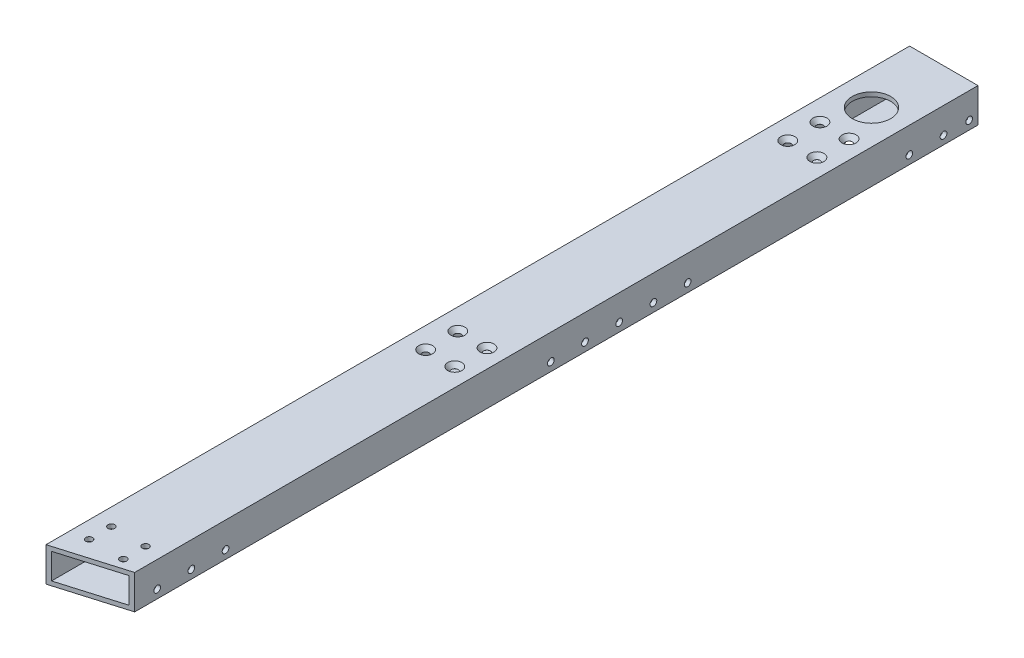
SolidWorks part; units mm, degrees
ref_plane "Front Plane" through (0, 0, 0) normal (0, 0, 1) x (1, 0, 0)
ref_plane "Top Plane" through (0, 0, 0) normal (0, 1, 0) x (1, 0, 0)
ref_plane "Right Plane" through (0, 0, 0) normal (1, 0, 0) x (0, 0, -1)
sketch "Sketch1" plane through (0, 0, 0) normal (0, 0, 1) x (1, 0, 0)
  line L0 (-22.225, 9.525) -> (22.225, 9.525)
  line L2 (-25.4, 12.7) -> (25.4, 12.7)
  line L3 (-25.4, 12.7) -> (-25.4, -12.7)
  line L4 (-25.4, -12.7) -> (25.4, -12.7)
  line L5 (25.4, 12.7) -> (25.4, -12.7)
  line L10 (22.225, 9.525) -> (22.225, -9.525)
  line L11 (-22.225, -9.525) -> (22.225, -9.525)
  line L12 (-22.225, 9.525) -> (-22.225, -9.525)
  point P12 (0, 12.7)
  point P14 (25.4, 0)
  dimension "Wall Thickness" = 3.175
  dimension "Outside Width" = 50.8
  dimension "Outside Height" = 25.4
  dimension "Inside Height" = 19.05
  dimension "Inside Width" = 44.45
sketch "Sketch2" plane through (0, 0, 0) normal (1, 0, 0) x (0, 0, -1)
  line L0 (320.675, 0) -> (-320.675, 0)
  point P4 (0, 0)
  point P7 (-320.675, 0)
  point P10 (320.675, 0)
  dimension "Length" = 641.35
sketch "Sketch3" plane through (0, 0, 0) normal (0, 0, 1) x (1, 0, 0)
  line L21 (25.4, 12.7) -> (-25.4, 12.7)
  line L22 (25.4, -12.7) -> (25.4, 12.7)
  line L23 (-25.4, -12.7) -> (25.4, -12.7)
  line L24 (-25.4, 12.7) -> (-25.4, -12.7)
  line L25 (25.4, 12.7) -> (-25.4, 12.7)
  line L26 (25.4, -12.7) -> (25.4, 12.7)
  line L27 (-25.4, -12.7) -> (25.4, -12.7)
  line L28 (-25.4, 12.7) -> (-25.4, -12.7)
  line L29 (22.225, 9.525) -> (-22.225, 9.525)
  line L30 (22.225, -9.525) -> (22.225, 9.525)
  line L31 (-22.225, -9.525) -> (22.225, -9.525)
  line L32 (-22.225, 9.525) -> (-22.225, -9.525)
  line L33 (22.225, 9.525) -> (-22.225, 9.525)
  line L34 (22.225, -9.525) -> (22.225, 9.525)
  line L35 (-22.225, -9.525) -> (22.225, -9.525)
  line L36 (-22.225, 9.525) -> (-22.225, -9.525)
  dimension "D1" = 0
  dimension "D2" = 0
extrude "Boss-Extrude1" add sketch "Sketch3" along normal up to vertex (320.675 mm away) and the other way up to vertex (320.675 mm away) up to point (0, 0, 320.675) other way up to point (0, 0, -320.675)
sketch "Drawing Reference" plane through (0, 0, 0) normal (1, 0, 0) x (0, 0, -1)
  line L0 (-320.675, 0) -> (320.675, 0) construction
  line L1 (0, -12.7) -> (0, 12.7) construction
  line L2 (-320.675, -12.7) -> (320.675, -12.7) construction
  line L5 (-320.675, 12.7) -> (320.675, 12.7) construction
  point P7 (-284.099, 0)
  point P8 (284.099, 0)
  dimension "D1" = 36.576
sketch "Sketch4" plane through (0, 12.7, 0) normal (0, 1, 0) x (1, 0, 0)
  line L0 (-25.4, -320.675) -> (25.4, -305.6274)
  line L1 (25.4, -320.675) -> (25.4, 320.675) construction
  line L2 (25.4, -320.675) -> (-25.4, -320.675)
  dimension "D1" = 16.5
extrude "Cut-Extrude1" cut sketch "Sketch4" against normal through all and the other way through all flip side to cut
sketch "Sketch8" plane through (0, 12.7, 0) normal (0, 1, 0) x (1, 0, 0)
  line L0 (0, 320.675) -> (0, 266.954) construction
  line L1 (25.4, 320.675) -> (-25.4, 320.675) construction
  circle A0 centre (0, 266.954) radius 14.2875
  dimension "D1" = 53.721
extrude "Cut-Extrude2" cut sketch "Sketch8" against normal through all
sketch "Sketch9" plane through (0, 12.7, 0) normal (0, 1, 0) x (1, 0, 0)
  line L0 (-12.7762, -284.753) -> (12.6238, -284.753) construction
  line L1 (12.6238, -284.753) -> (12.6238, -301.263) construction
  line L2 (12.6238, -301.263) -> (-12.7762, -301.263) construction
  line L3 (-12.7762, -301.263) -> (-12.7762, -284.753) construction
hole_wizard "#10 Clearance Hole1" positions "Sketch10" profile "Sketch11" hole size "#10" standard "ANSI Inch"
sketch "Sketch10" plane through (0, 12.7, 0) normal (0, 1, 0) x (1, 0, 0)
  point P0 (-12.7762, -284.753)
  point P3 (12.6238, -284.753)
  point P6 (12.6238, -301.263)
  point P9 (-12.7762, -301.263)
sketch "Sketch11" plane through (-12.7762, 12.7, 284.753) normal (1, 0, 0) x (0, 0, 1)
  line L0 (0, 0) -> (0, 6.5757)
  line L1 (0, 6.5757) -> (2.4892, 5.08)
  line L2 (2.4892, 5.08) -> (2.4892, 0)
  line L5 (2.4892, 0) -> (0, 0)
  line L10 (0, 6.5757) -> (-2.4892, 5.08) construction
  line L11 (0, -6.35) -> (0, 107.95) construction
  dimension "Hole Dia." = 4.9784
  dimension "Hole Depth" = 5.08
  dimension "Drill Angle" = 118
hole_wizard "#10 Clearance Hole2" positions "Sketch12" profile "Sketch13" hole size "#10" standard "ANSI Inch" end condition through all
sketch "Sketch12" plane through (25.4, 0, 0) normal (1, 0, 0) x (0, 0, -1)
  point P9 (3.429, -6.35)
  point P12 (28.829, -6.35)
  point P15 (54.229, -6.35)
  point P18 (79.629, -6.35)
  point P21 (105.029, -6.35)
  point P24 (-288.925, -6.35)
  point P27 (-263.525, -6.35)
  point P30 (-238.1261, -6.3882)
sketch "Sketch13" plane through (25.4, -6.35, -3.429) normal (0, 1, 0) x (0, 0, -1)
  line L0 (0, 0) -> (0, 50.8)
  line L1 (0, 50.8) -> (2.4892, 50.8)
  line L2 (2.4892, 50.8) -> (2.4892, 0)
  line L5 (2.4892, 0) -> (0, 0)
  line L11 (0, -6.35) -> (0, 107.95) construction
  dimension "Thru Hole Dia." = 4.9784
  dimension "Thru Hole Depth" = 50.8
hole_wizard "#10 Clearance Hole3" positions "Sketch14" profile "Sketch15" hole size "#10" standard "ANSI Inch"
sketch "Sketch14" plane through (25.4, 0, 0) normal (1, 0, 0) x (0, 0, -1)
  point P0 (269.6733, -6.3882)
  point P3 (295.0733, -6.3882)
  point P6 (314.1233, -6.3882)
sketch "Sketch15" plane through (25.4, -6.3882, -269.6733) normal (0, 1, 0) x (0, 0, -1)
  line L0 (0, 0) -> (0, 4.7977)
  line L1 (0, 4.7977) -> (2.4892, 3.302)
  line L2 (2.4892, 3.302) -> (2.4892, 0)
  line L5 (2.4892, 0) -> (0, 0)
  line L10 (0, 4.7977) -> (-2.4892, 3.302) construction
  line L11 (0, -6.35) -> (0, 107.95) construction
  dimension "Hole Dia." = 4.9784
  dimension "Hole Depth" = 3.302
  dimension "Drill Angle" = 118
sketch "Sketch16" plane through (0, -12.7, 0) normal (0, -1, 0) x (1, 0, 0)
  line L0 (0, -266.954) -> (12.752, -254.202) construction
hole_wizard "Tap Drill for #8-32 Tap1" positions "Sketch17" profile "Sketch18" hole size "#8-32" standard "ANSI Inch"
sketch "Sketch17" plane through (0, -12.7, 0) normal (0, -1, 0) x (-1, 0, 0)
  point P0 (-12.752, 254.202)
sketch "Sketch18" plane through (12.752, -12.7, -254.202) normal (1, 0, 0) x (0, 0, -1)
  line L0 (0, 0) -> (0, 6.1178)
  line L1 (0, 6.1178) -> (1.7272, 5.08)
  line L2 (1.7272, 5.08) -> (1.7272, 0)
  line L5 (1.7272, 0) -> (0, 0)
  line L10 (0, 6.1178) -> (-1.7272, 5.08) construction
  line L11 (0, -6.35) -> (0, 107.95) construction
  dimension "Hole Dia." = 3.4544
  dimension "Hole Depth" = 5.08
  dimension "Drill Angle" = 118
hole_wizard "#10 Clearance Hole4" positions "Sketch20" profile "Sketch21" hole size "#10" standard "ANSI Inch" end condition through all
sketch "Sketch20" plane through (0, -12.7, 0) normal (0, -1, 0) x (-1, 0, 0)
  point P0 (-11.8451, -30.4483)
  point P3 (9.7957, -30.4483)
  point P6 (9.7957, -54.3243)
  point P9 (-11.8451, -54.3243)
  point P12 (-11.8451, 214.5982)
  point P15 (9.7957, 214.5982)
  point P18 (-11.8451, 238.4742)
  point P21 (9.7957, 238.4742)
sketch "Sketch21" plane through (11.8451, -12.7, 30.4483) normal (1, 0, 0) x (0, 0, -1)
  line L0 (0, 0) -> (0, 25.4)
  line L1 (0, 25.4) -> (5.2197, 25.4)
  line L2 (2.4892, 22.2589) -> (2.4892, 0)
  line L5 (2.4892, 0) -> (0, 0)
  line L7 (5.2197, 25.4) -> (2.4892, 22.2589)
  line L8 (-5.2197, 25.4) -> (-2.4892, 22.2589) construction
  line L11 (0, -6.35) -> (0, 107.95) construction
  dimension "Thru Hole Dia." = 4.9784
  dimension "Thru Hole Depth" = 25.4
  dimension "Far C'Sink Dia." = 10.4394
  dimension "Far C'Sink Angle" = 82
equation "\"D1@Drawing Reference\"=\"Outside Width@Sketch1\" * 0.72"
